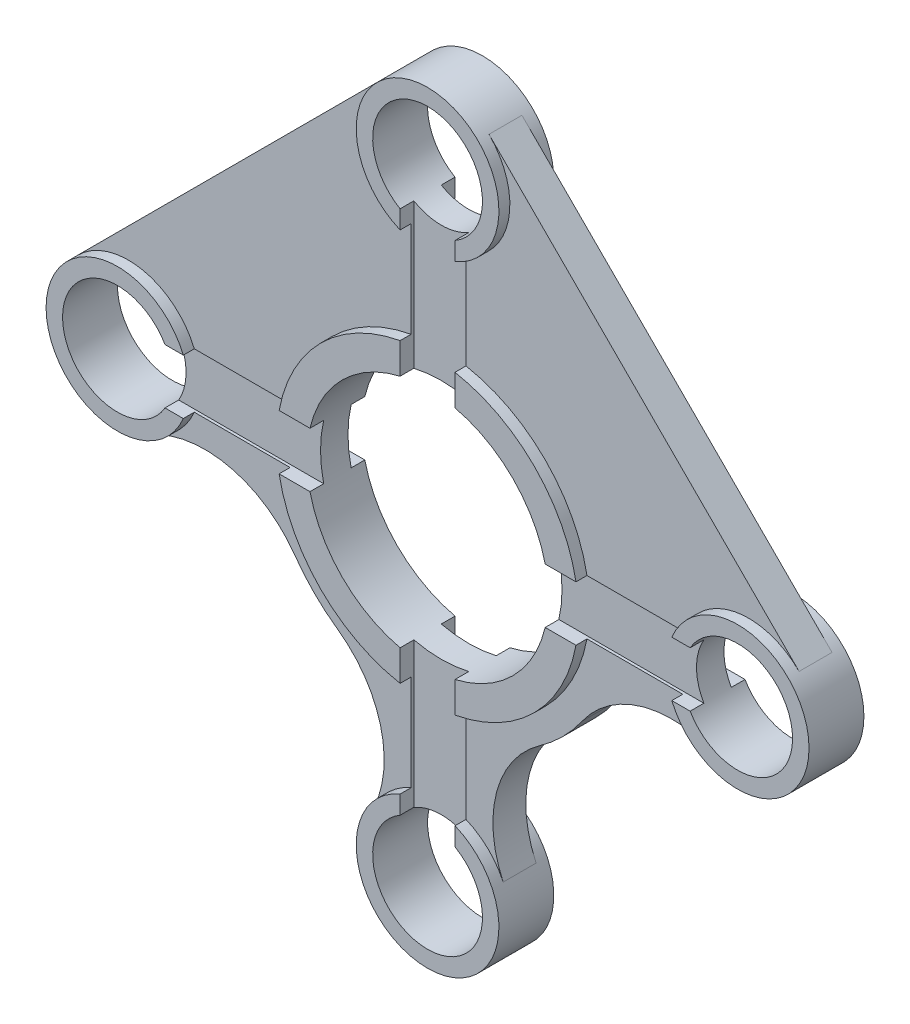
SolidWorks part; units mm, degrees
ref_plane "Front Plane" through (0, 0, 0) normal (0, 0, 1) x (1, 0, 0)
ref_plane "Top Plane" through (0, 0, 0) normal (0, 1, 0) x (1, 0, 0)
ref_plane "Right Plane" through (0, 0, 0) normal (1, 0, 0) x (0, 0, -1)
sketch "Sketch1" plane through (0, 0, 0) normal (0, 0, 1) x (1, 0, 0)
  line L0 (0, 0) -> (88289.2373, 0) construction
  line L1 (0, 0) -> (0, 88289.2373) construction
  line L2 (-95.6795, 10) -> (-42.8486, 10)
  line L3 (-95.6795, -10) -> (-42.8486, -10)
  line L4 (10, 95.6795) -> (10, 42.8486)
  line L5 (-10, 95.6795) -> (-10, 42.8486)
  line L6 (95.6795, -10) -> (42.8486, -10)
  line L7 (95.6795, 10) -> (42.8486, 10)
  line L8 (-10, -95.6795) -> (-10, -42.8486)
  line L9 (10, -95.6795) -> (10, -42.8486)
  line L10 (-131.3848, 18.3848) -> (-18.3848, 131.3848)
  line L11 (131.3848, 18.3848) -> (18.3848, 131.3848)
  circle A0 centre (0, 0) radius 44
  arc A1 (-54.0833, -10) -> (-10, -54.0833) centre (0, 0) ccw
  circle A2 centre (0, 0) radius 113 construction
  circle A3 centre (-113, 0) radius 20
  arc A4 (-89, 10) -> (-89, -10) centre (-113, 0) ccw
  circle A5 centre (0, 113) radius 20
  arc A6 (10, 89) -> (-10, 89) centre (0, 113) ccw
  circle A7 centre (113, 0) radius 20
  arc A8 (89, -10) -> (89, 10) centre (113, 0) ccw
  circle A9 centre (0, -113) radius 20
  arc A10 (-10, -89) -> (10, -89) centre (0, -113) ccw
  arc A11 (-10, 54.0833) -> (-54.0833, 10) centre (0, 0) ccw
  arc A12 (54.0833, 10) -> (10, 54.0833) centre (0, 0) ccw
  arc A13 (10, -54.0833) -> (54.0833, -10) centre (0, 0) ccw
  arc A14 (-52.3594, -36.8034) -> (-102.0028, -23.5598) centre (-85.0841, -59.8055) ccw
  arc A15 (-23.5598, -102.0028) -> (-36.8034, -52.3594) centre (-59.8055, -85.0841) ccw
  arc A16 (-52.3594, -36.8034) -> (-36.8034, -52.3594) centre (0, 0) ccw
  arc A17 (23.5598, -102.0028) -> (36.8034, -52.3594) centre (59.8055, -85.0841) cw
  arc A18 (52.3594, -36.8034) -> (36.8034, -52.3594) centre (0, 0) cw
  arc A19 (52.3594, -36.8034) -> (102.0028, -23.5598) centre (85.0841, -59.8055) cw
  point P45 (0, 0)
  dimension "D1" = 110
  dimension "D2" = 88
  dimension "D3" = 226
  dimension "D4" = 40
  dimension "D5" = 52
  dimension "D8" = 80
  dimension "D9" = 80
  dimension "D10" = 128
  dimension "D6" = 20
  dimension "D7" = 4
extrude "Boss-Extrude1" add sketch "Sketch1" along normal mid plane 10 contours A5 L5 A0 L4 | A3 L3 A0 L2 | A7 L7 A0 L6 | A9 L9 A0 L8 region at (-68.748, 0, 0) region at (0, 68.748, 0) region at (0, -68.748, 0) region at (68.748, 0, 0)
extrude "Boss-Extrude2" add sketch "Sketch1<3>" along normal mid plane 20 contours L5 A11 L2 A0 | L7 A12 L4 A0 | L9 A13 L6 A0 | L3 A1 L8 A0 region at (-33.2351, 33.2351, 0) region at (-33.2351, -33.2351, 0) region at (33.2351, 33.2351, 0) region at (33.2351, -33.2351, 0)
sketch "Sketch1<3>" plane through (0, 0, 0) normal (0, 0, 1) x (1, 0, 0) same geometry as "Sketch1"
extrude "Boss-Extrude3" add sketch "Sketch1<4>" along normal mid plane 12 contours A11 L5 A6 L10 A4 L2 | A12 L7 A8 L11 A6 L4 | A18 A19 A8 L6 A13 L9 A10 A17 | A14 A16 A15 A10 L8 A1 L3 A4 region at (-57.0044, 57.0044, 0) region at (-43.0084, -43.0084, 0) region at (57.0044, 57.0044, 0) region at (43.0084, -43.0084, 0)
sketch "Sketch1<4>" plane through (0, 0, 0) normal (0, 0, 1) x (1, 0, 0) same geometry as "Sketch1"
extrude "Boss-Extrude4" add sketch "Sketch1<5>" along normal mid plane 20 contours A6 L5 A5 L4 | L2 A4 L3 A3 | A8 L7 A7 L6 | L8 A10 L9 A9 region at (-133.7214, 0, 0) region at (0, 138.2786, 0) region at (133.7042, -14.5032, 0) region at (-10.7214, -92.3397, 0)
sketch "Sketch1<5>" plane through (0, 0, 0) normal (0, 0, 1) x (1, 0, 0) same geometry as "Sketch1"
